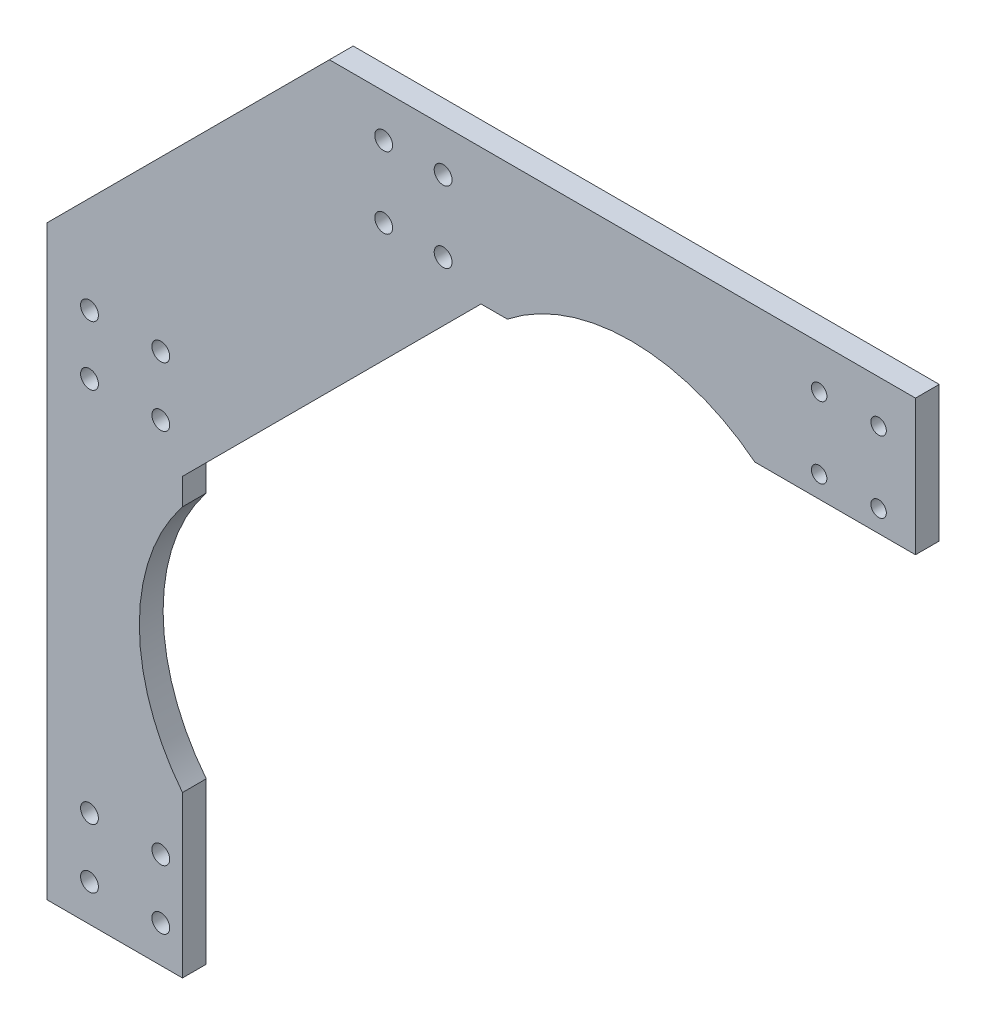
SolidWorks part; units mm, degrees
ref_plane "Front Plane" through (0, 0, 0) normal (0, 0, 1) x (1, 0, 0)
ref_plane "Top Plane" through (0, 0, 0) normal (0, 1, 0) x (1, 0, 0)
ref_plane "Right Plane" through (0, 0, 0) normal (1, 0, 0) x (0, 0, -1)
sketch "Sketch1" plane through (0, 0, 0) normal (0, 0, 1) x (1, 0, 0)
  line L0 (0, 0) -> (0, 75.4924) construction
  line L1 (-98.3263, -47.8405) -> (-75.4924, -47.8405)
  line L2 (-98.3263, -47.8405) -> (-98.3263, 50.769)
  line L4 (-75.4924, -47.8405) -> (-75.4924, 25.2528) construction
  line L5 (-50.769, 98.3263) -> (47.8405, 98.3263)
  line L7 (-25.2528, 75.4924) -> (47.8405, 75.4924) construction
  line L8 (47.8405, 98.3263) -> (47.8405, 75.4924)
  line L9 (0, 0) -> (-75.4924, 0) construction
  line L10 (-25.2528, 75.4924) -> (-75.4924, 25.2528)
  line L11 (-75.4924, 75.4924) -> (-25.2528, 75.4924) construction
  line L12 (-75.4924, 25.2528) -> (-75.4924, 75.4924) construction
  line L13 (-50.769, 98.3263) -> (-98.3263, 50.769)
  line L14 (-98.3263, 98.3263) -> (-50.769, 98.3263) construction
  line L15 (-98.3263, 50.769) -> (-98.3263, 98.3263) construction
  line L16 (-20.8161, 75.4924) -> (-25.2528, 75.4924)
  line L17 (20.8161, 75.4924) -> (47.8405, 75.4924)
  line L18 (-75.4924, 25.2528) -> (-75.4924, 20.8161)
  line L19 (-75.4924, -47.8405) -> (-75.4924, -20.8161)
  line L20 (-75.4924, 20.8161) -> (-75.4924, -20.8161) construction
  line L21 (-20.8161, 75.4924) -> (20.8161, 75.4924) construction
  arc A0 (20.8161, 75.4924) -> (-20.8161, 75.4924) centre (0, 49.2714) ccw
  arc A1 (-75.4924, 20.8161) -> (-75.4924, -20.8161) centre (-49.2714, 0) ccw
  point P11 (47.8405, 98.0191)
  point P15 (-98.3263, 50.769)
  dimension "D1" = 135
extrude "Boss-Extrude1" add sketch "Sketch1" along normal blind 4
ref_axis "Axis1" through (0, 0, -0.2) along (0, 0, 1)
sketch "Sketch3" plane through (0, 0, 4) normal (0, 0, 1) x (1, 0, 0)
  line L0 (-91.1351, 41.6359) -> (-91.1351, 31.6359) construction
  line L1 (-91.1351, -31.6359) -> (-91.1351, -41.6359) construction
  line L2 (-91.1351, -31.6359) -> (-79.1351, -31.6359) construction
  line L3 (-79.1351, -31.6359) -> (-79.1351, -41.6359) construction
  line L4 (-91.1351, -41.6359) -> (-79.1351, -41.6359) construction
  line L5 (-91.1351, 41.6359) -> (-79.1351, 41.6359) construction
  line L6 (-79.1351, 41.6359) -> (-79.1351, 31.6359) construction
  line L7 (-91.1351, 31.6359) -> (-79.1351, 31.6359) construction
  line L8 (31.6359, 91.1351) -> (31.6359, 79.1351) construction
  line L9 (31.6359, 91.1351) -> (41.6359, 91.1351) construction
  line L10 (41.6359, 91.1351) -> (41.6359, 79.1351) construction
  line L11 (31.6359, 79.1351) -> (41.6359, 79.1351) construction
  line L12 (-31.6359, 91.1351) -> (-31.6359, 79.1351) construction
  line L13 (-31.6359, 91.1351) -> (-41.6359, 91.1351) construction
  line L14 (-41.6359, 91.1351) -> (-41.6359, 79.1351) construction
  line L15 (-31.6359, 79.1351) -> (-41.6359, 79.1351) construction
  circle A0 centre (-91.1351, -41.6359) radius 1.5
  circle A1 centre (-91.1351, -31.6359) radius 1.5
  circle A2 centre (-79.1351, -31.6359) radius 1.5
  circle A3 centre (-79.1351, -41.6359) radius 1.5
  circle A4 centre (-91.1351, 31.6359) radius 1.5
  circle A5 centre (-91.1351, 41.6359) radius 1.5
  circle A6 centre (-79.1351, 41.6359) radius 1.5
  circle A7 centre (-79.1351, 31.6359) radius 1.5
  circle A8 centre (31.6359, 79.1351) radius 1.3
  circle A9 centre (31.6359, 91.1351) radius 1.3
  circle A10 centre (41.6359, 91.1351) radius 1.3
  circle A11 centre (41.6359, 79.1351) radius 1.3
  circle A12 centre (-31.6359, 79.1351) radius 1.5
  circle A13 centre (-31.6359, 91.1351) radius 1.5
  circle A14 centre (-41.6359, 91.1351) radius 1.5
  circle A15 centre (-41.6359, 79.1351) radius 1.5
  point P8 (-79.1351, -31.6359)
  point P9 (-91.1351, -41.6359)
  point P10 (-79.1351, -41.6359)
  point P11 (-91.1351, -31.6359)
  point P12 (-79.3354, -41.5254)
  point P13 (-91.1351, -41.6359)
  point P14 (-79.1351, -31.6359)
  point P15 (0, 0)
  point P16 (-91.1351, -41.6359)
  point P41 (-85.9129, 28.3795)
  point P42 (-91.0989, 31.6107)
  point P43 (-78.7076, 41.4703)
  point P44 (-79.1671, 41.6142)
  point P45 (-91.1351, 31.6359)
  point P46 (-79.1351, 41.6359)
  point P47 (-41.6359, 79.1351)
  point P48 (-31.6359, 91.1351)
  point P49 (41.6359, 91.1351)
  point P50 (31.6359, 79.1351)
  dimension "D1" = 3
  dimension "D2" = 3
  dimension "D3" = 2.6
  dimension "D4" = 3
extrude "Cut-Extrude1" cut sketch "Sketch3" against normal blind 10
